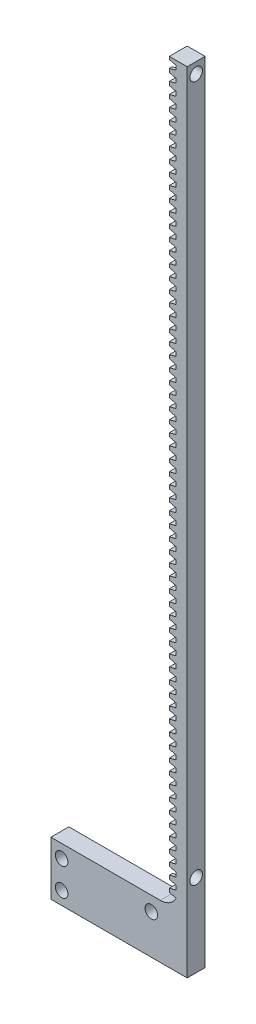
SolidWorks part; units mm, degrees
ref_plane "前视基准面" through (0, 0, 0) normal (0, 0, 1) x (1, 0, 0)
ref_plane "上视基准面" through (0, 0, 0) normal (0, 1, 0) x (1, 0, 0)
ref_plane "右视基准面" through (0, 0, 0) normal (1, 0, 0) x (0, 0, -1)
sketch "草图1" plane through (0, 0, 0) normal (0, 0, 1) x (1, 0, 0)
  line L0 (0, 0) -> (-38, 0)
  line L1 (-38, 0) -> (-38, 15)
  line L2 (-38, 15) -> (-3.0528, 15)
  line L3 (-3, 15) -> (-3, 220) construction
  line L4 (-3, 220) -> (0, 220)
  line L5 (0, 220) -> (0, 0)
  line L6 (-3.0528, 218.7619) -> (-3.0528, 217.6097)
  line L7 (-3.0528, 217.6097) -> (-5, 217.1061)
  line L8 (-5, 217.1061) -> (-5, 216.1239)
  line L9 (-5, 216.1239) -> (-3.0528, 215.6204)
  line L10 (-3.0528, 215.6204) -> (-3.0528, 214.4681)
  line L11 (-3.0528, 214.4681) -> (-5, 213.9645)
  line L12 (-5, 213.9645) -> (-5, 212.9823)
  line L13 (-5, 212.9823) -> (-3.0528, 212.4788)
  line L14 (-3.0528, 212.4788) -> (-3.0528, 211.3265)
  line L15 (-3.0528, 211.3265) -> (-5, 210.8229)
  line L16 (-5, 210.8229) -> (-5, 209.8407)
  line L17 (-5, 209.8407) -> (-3.0528, 209.3372)
  line L18 (-3.0528, 209.3372) -> (-3.0528, 208.1849)
  line L19 (-3.0528, 208.1849) -> (-5, 207.6813)
  line L20 (-5, 207.6813) -> (-5, 206.6992)
  line L21 (-5, 206.6992) -> (-3.0528, 206.1956)
  line L22 (-3.0528, 206.1956) -> (-3.0528, 205.0433)
  line L23 (-3.0528, 205.0433) -> (-5, 204.5397)
  line L24 (-5, 204.5397) -> (-5, 203.5576)
  line L25 (-5, 203.5576) -> (-3.0528, 203.054)
  line L26 (-3.0528, 203.054) -> (-3.0528, 201.9017)
  line L27 (-3.0528, 201.9017) -> (-5, 201.3981)
  line L28 (-5, 201.3981) -> (-5, 200.416)
  line L29 (-5, 200.416) -> (-3.0528, 199.9124)
  line L30 (-3.0528, 199.9124) -> (-3.0528, 198.7601)
  line L31 (-3.0528, 198.7601) -> (-5, 198.2566)
  line L32 (-5, 198.2566) -> (-5, 197.2744)
  line L33 (-5, 197.2744) -> (-3.0528, 196.7708)
  line L34 (-3.0528, 196.7708) -> (-3.0528, 195.6185)
  line L35 (-3.0528, 195.6185) -> (-5, 195.115)
  line L36 (-5, 195.115) -> (-5, 194.1328)
  line L37 (-5, 194.1328) -> (-3.0528, 193.6292)
  line L38 (-3.0528, 193.6292) -> (-3.0528, 192.477)
  line L39 (-3.0528, 192.477) -> (-5, 191.9734)
  line L40 (-5, 191.9734) -> (-5, 190.9912)
  line L41 (-5, 190.9912) -> (-3.0528, 190.4876)
  line L42 (-3.0528, 190.4876) -> (-3.0528, 189.3354)
  line L43 (-3.0528, 189.3354) -> (-5, 188.8318)
  line L44 (-5, 188.8318) -> (-5, 187.8496)
  line L45 (-5, 187.8496) -> (-3.0528, 187.346)
  line L46 (-3.0528, 187.346) -> (-3.0528, 186.1938)
  line L47 (-3.0528, 186.1938) -> (-5, 185.6902)
  line L48 (-5, 185.6902) -> (-5, 184.708)
  line L49 (-5, 184.708) -> (-3.0528, 184.2044)
  line L50 (-3.0528, 184.2044) -> (-3.0528, 183.0522)
  line L51 (-3.0528, 183.0522) -> (-5, 182.5486)
  line L52 (-5, 182.5486) -> (-5, 181.5664)
  line L53 (-5, 181.5664) -> (-3.0528, 181.0628)
  line L54 (-3.0528, 181.0628) -> (-3.0528, 179.9106)
  line L55 (-3.0528, 179.9106) -> (-5, 179.407)
  line L56 (-5, 179.407) -> (-5, 178.4248)
  line L57 (-5, 178.4248) -> (-3.0528, 177.9212)
  line L58 (-3.0528, 177.9212) -> (-3.0528, 176.769)
  line L59 (-3.0528, 176.769) -> (-5, 176.2654)
  line L60 (-5, 176.2654) -> (-5, 175.2832)
  line L61 (-5, 175.2832) -> (-3.0528, 174.7796)
  line L62 (-3.0528, 174.7796) -> (-3.0528, 173.6274)
  line L63 (-3.0528, 173.6274) -> (-5, 173.1238)
  line L64 (-5, 173.1238) -> (-5, 172.1416)
  line L65 (-5, 172.1416) -> (-3.0528, 171.6381)
  line L66 (-3.0528, 171.6381) -> (-3.0528, 170.4858)
  line L67 (-3.0528, 170.4858) -> (-5, 169.9822)
  line L68 (-5, 169.9822) -> (-5, 169)
  line L69 (-5, 169) -> (-3.0528, 168.4965)
  line L70 (-3.0528, 168.4965) -> (-3.0528, 167.3442)
  line L71 (-3.0528, 167.3442) -> (-5, 166.8406)
  line L72 (-5, 166.8406) -> (-5, 165.8585)
  line L73 (-5, 165.8585) -> (-3.0528, 165.3549)
  line L74 (-3.0528, 165.3549) -> (-3.0528, 164.2026)
  line L75 (-3.0528, 164.2026) -> (-5, 163.699)
  line L76 (-5, 163.699) -> (-5, 162.7169)
  line L77 (-5, 162.7169) -> (-3.0528, 162.2133)
  line L78 (-3.0528, 162.2133) -> (-3.0528, 161.061)
  line L79 (-3.0528, 161.061) -> (-5, 160.5574)
  line L80 (-5, 160.5574) -> (-5, 159.5753)
  line L81 (-5, 159.5753) -> (-3.0528, 159.0717)
  line L82 (-3.0528, 159.0717) -> (-3.0528, 157.9194)
  line L83 (-3.0528, 157.9194) -> (-5, 157.4159)
  line L84 (-5, 157.4159) -> (-5, 156.4337)
  line L85 (-5, 156.4337) -> (-3.0528, 155.9301)
  line L86 (-3.0528, 155.9301) -> (-3.0528, 154.7778)
  line L87 (-3.0528, 154.7778) -> (-5, 154.2743)
  line L88 (-5, 154.2743) -> (-5, 153.2921)
  line L89 (-5, 153.2921) -> (-3.0528, 152.7885)
  line L90 (-3.0528, 152.7885) -> (-3.0528, 151.6362)
  line L91 (-3.0528, 151.6362) -> (-5, 151.1327)
  line L92 (-5, 151.1327) -> (-5, 150.1505)
  line L93 (-5, 150.1505) -> (-3.0528, 149.6469)
  line L94 (-3.0528, 149.6469) -> (-3.0528, 148.4947)
  line L95 (-3.0528, 148.4947) -> (-5, 147.9911)
  line L96 (-5, 147.9911) -> (-5, 147.0089)
  line L97 (-5, 147.0089) -> (-3.0528, 146.5053)
  line L98 (-3.0528, 146.5053) -> (-3.0528, 145.3531)
  line L99 (-3.0528, 145.3531) -> (-5, 144.8495)
  line L100 (-5, 144.8495) -> (-5, 143.8673)
  line L101 (-5, 143.8673) -> (-3.0528, 143.3637)
  line L102 (-3.0528, 143.3637) -> (-3.0528, 142.2115)
  line L103 (-3.0528, 142.2115) -> (-5, 141.7079)
  line L104 (-5, 141.7079) -> (-5, 140.7257)
  line L105 (-5, 140.7257) -> (-3.0528, 140.2221)
  line L106 (-3.0528, 140.2221) -> (-3.0528, 139.0699)
  line L107 (-3.0528, 139.0699) -> (-5, 138.5663)
  line L108 (-5, 138.5663) -> (-5, 137.5841)
  line L109 (-5, 137.5841) -> (-3.0528, 137.0805)
  line L110 (-3.0528, 137.0805) -> (-3.0528, 135.9283)
  line L111 (-3.0528, 135.9283) -> (-5, 135.4247)
  line L112 (-5, 135.4247) -> (-5, 134.4425)
  line L113 (-5, 134.4425) -> (-3.0528, 133.9389)
  line L114 (-3.0528, 133.9389) -> (-3.0528, 132.7867)
  line L115 (-3.0528, 132.7867) -> (-5, 132.2831)
  line L116 (-5, 132.2831) -> (-5, 131.3009)
  line L117 (-5, 131.3009) -> (-3.0528, 130.7974)
  line L118 (-3.0528, 130.7974) -> (-3.0528, 129.6451)
  line L119 (-3.0528, 129.6451) -> (-5, 129.1415)
  line L120 (-5, 129.1415) -> (-5, 128.1593)
  line L121 (-5, 128.1593) -> (-3.0528, 127.6558)
  line L122 (-3.0528, 127.6558) -> (-3.0528, 126.5035)
  line L123 (-3.0528, 126.5035) -> (-5, 125.9999)
  line L124 (-5, 125.9999) -> (-5, 125.0177)
  line L125 (-5, 125.0177) -> (-3.0528, 124.5142)
  line L126 (-3.0528, 124.5142) -> (-3.0528, 123.3619)
  line L127 (-3.0528, 123.3619) -> (-5, 122.8583)
  line L128 (-5, 122.8583) -> (-5, 121.8762)
  line L129 (-5, 121.8762) -> (-3.0528, 121.3726)
  line L130 (-3.0528, 121.3726) -> (-3.0528, 120.2203)
  line L131 (-3.0528, 120.2203) -> (-5, 119.7167)
  line L132 (-5, 119.7167) -> (-5, 118.7346)
  line L133 (-5, 118.7346) -> (-3.0528, 118.231)
  line L134 (-3.0528, 118.231) -> (-3.0528, 117.0787)
  line L135 (-3.0528, 117.0787) -> (-5, 116.5751)
  line L136 (-5, 116.5751) -> (-5, 115.593)
  line L137 (-5, 115.593) -> (-3.0528, 115.0894)
  line L138 (-3.0528, 115.0894) -> (-3.0528, 113.9371)
  line L139 (-3.0528, 113.9371) -> (-5, 113.4336)
  line L140 (-5, 113.4336) -> (-5, 112.4514)
  line L141 (-5, 112.4514) -> (-3.0528, 111.9478)
  line L142 (-3.0528, 111.9478) -> (-3.0528, 110.7955)
  line L143 (-3.0528, 110.7955) -> (-5, 110.292)
  line L144 (-5, 110.292) -> (-5, 109.3098)
  line L145 (-5, 109.3098) -> (-3.0528, 108.8062)
  line L146 (-3.0528, 108.8062) -> (-3.0528, 107.654)
  line L147 (-3.0528, 107.654) -> (-5, 107.1504)
  line L148 (-5, 107.1504) -> (-5, 106.1682)
  line L149 (-5, 106.1682) -> (-3.0528, 105.6646)
  line L150 (-3.0528, 105.6646) -> (-3.0528, 104.5124)
  line L151 (-3.0528, 104.5124) -> (-5, 104.0088)
  line L152 (-5, 104.0088) -> (-5, 103.0266)
  line L153 (-5, 103.0266) -> (-3.0528, 102.523)
  line L154 (-3.0528, 102.523) -> (-3.0528, 101.3708)
  line L155 (-3.0528, 101.3708) -> (-5, 100.8672)
  line L156 (-5, 100.8672) -> (-5, 99.885)
  line L157 (-5, 99.885) -> (-3.0528, 99.3814)
  line L158 (-3.0528, 99.3814) -> (-3.0528, 98.2292)
  line L159 (-3.0528, 98.2292) -> (-5, 97.7256)
  line L160 (-5, 97.7256) -> (-5, 96.7434)
  line L161 (-5, 96.7434) -> (-3.0528, 96.2398)
  line L162 (-3.0528, 96.2398) -> (-3.0528, 95.0876)
  line L163 (-3.0528, 95.0876) -> (-5, 94.584)
  line L164 (-5, 94.584) -> (-5, 93.6018)
  line L165 (-5, 93.6018) -> (-3.0528, 93.0982)
  line L166 (-3.0528, 93.0982) -> (-3.0528, 91.946)
  line L167 (-3.0528, 91.946) -> (-5, 91.4424)
  line L168 (-5, 91.4424) -> (-5, 90.4602)
  line L169 (-5, 90.4602) -> (-3.0528, 89.9566)
  line L170 (-3.0528, 89.9566) -> (-3.0528, 88.8044)
  line L171 (-3.0528, 88.8044) -> (-5, 88.3008)
  line L172 (-5, 88.3008) -> (-5, 87.3186)
  line L173 (-5, 87.3186) -> (-3.0528, 86.8151)
  line L174 (-3.0528, 86.8151) -> (-3.0528, 85.6628)
  line L175 (-3.0528, 85.6628) -> (-5, 85.1592)
  line L176 (-5, 85.1592) -> (-5, 84.177)
  line L177 (-5, 84.177) -> (-3.0528, 83.6735)
  line L178 (-3.0528, 83.6735) -> (-3.0528, 82.5212)
  line L179 (-3.0528, 82.5212) -> (-5, 82.0176)
  line L180 (-5, 82.0176) -> (-5, 81.0354)
  line L181 (-5, 81.0354) -> (-3.0528, 80.5319)
  line L182 (-3.0528, 80.5319) -> (-3.0528, 79.3796)
  line L183 (-3.0528, 79.3796) -> (-5, 78.876)
  line L184 (-5, 78.876) -> (-5, 77.8939)
  line L185 (-5, 77.8939) -> (-3.0528, 77.3903)
  line L186 (-3.0528, 77.3903) -> (-3.0528, 76.238)
  line L187 (-3.0528, 76.238) -> (-5, 75.7344)
  line L188 (-5, 75.7344) -> (-5, 74.7523)
  line L189 (-5, 74.7523) -> (-3.0528, 74.2487)
  line L190 (-3.0528, 74.2487) -> (-3.0528, 73.0964)
  line L191 (-3.0528, 73.0964) -> (-5, 72.5929)
  line L192 (-5, 72.5929) -> (-5, 71.6107)
  line L193 (-5, 71.6107) -> (-3.0528, 71.1071)
  line L194 (-3.0528, 71.1071) -> (-3.0528, 69.9548)
  line L195 (-3.0528, 69.9548) -> (-5, 69.4513)
  line L196 (-5, 69.4513) -> (-5, 68.4691)
  line L197 (-5, 68.4691) -> (-3.0528, 67.9655)
  line L198 (-3.0528, 67.9655) -> (-3.0528, 66.8132)
  line L199 (-3.0528, 66.8132) -> (-5, 66.3097)
  line L200 (-5, 66.3097) -> (-5, 65.3275)
  line L201 (-5, 65.3275) -> (-3.0528, 64.8239)
  line L202 (-3.0528, 64.8239) -> (-3.0528, 63.6717)
  line L203 (-3.0528, 63.6717) -> (-5, 63.1681)
  line L204 (-5, 63.1681) -> (-5, 62.1859)
  line L205 (-5, 62.1859) -> (-3.0528, 61.6823)
  line L206 (-3.0528, 61.6823) -> (-3.0528, 60.5301)
  line L207 (-3.0528, 60.5301) -> (-5, 60.0265)
  line L208 (-5, 60.0265) -> (-5, 59.0443)
  line L209 (-5, 59.0443) -> (-3.0528, 58.5407)
  line L210 (-3.0528, 58.5407) -> (-3.0528, 57.3885)
  line L211 (-3.0528, 57.3885) -> (-5, 56.8849)
  line L212 (-5, 56.8849) -> (-5, 55.9027)
  line L213 (-5, 55.9027) -> (-3.0528, 55.3991)
  line L214 (-3.0528, 55.3991) -> (-3.0528, 54.2469)
  line L215 (-3.0528, 54.2469) -> (-5, 53.7433)
  line L216 (-5, 53.7433) -> (-5, 52.7611)
  line L217 (-5, 52.7611) -> (-3.0528, 52.2575)
  line L218 (-3.0528, 52.2575) -> (-3.0528, 51.1053)
  line L219 (-3.0528, 51.1053) -> (-5, 50.6017)
  line L220 (-5, 50.6017) -> (-5, 49.6195)
  line L221 (-5, 49.6195) -> (-3.0528, 49.1159)
  line L222 (-3.0528, 49.1159) -> (-3.0528, 47.9637)
  line L223 (-3.0528, 47.9637) -> (-5, 47.4601)
  line L224 (-5, 47.4601) -> (-5, 46.4779)
  line L225 (-5, 46.4779) -> (-3.0528, 45.9743)
  line L226 (-3.0528, 45.9743) -> (-3.0528, 44.8221)
  line L227 (-3.0528, 44.8221) -> (-5, 44.3185)
  line L228 (-5, 44.3185) -> (-5, 43.3363)
  line L229 (-5, 43.3363) -> (-3.0528, 42.8328)
  line L230 (-3.0528, 42.8328) -> (-3.0528, 41.6805)
  line L231 (-3.0528, 41.6805) -> (-5, 41.1769)
  line L232 (-5, 41.1769) -> (-5, 40.1947)
  line L233 (-5, 40.1947) -> (-3.0528, 39.6912)
  line L234 (-3.0528, 39.6912) -> (-3.0528, 38.5389)
  line L235 (-3.0528, 38.5389) -> (-5, 38.0353)
  line L236 (-5, 38.0353) -> (-5, 37.0532)
  line L237 (-5, 37.0532) -> (-3.0528, 36.5496)
  line L238 (-3.0528, 36.5496) -> (-3.0528, 35.3973)
  line L239 (-3.0528, 35.3973) -> (-5, 34.8937)
  line L240 (-5, 34.8937) -> (-5, 33.9116)
  line L241 (-5, 33.9116) -> (-3.0528, 33.408)
  line L242 (-3.0528, 33.408) -> (-3.0528, 32.2557)
  line L243 (-3.0528, 32.2557) -> (-5, 31.7521)
  line L244 (-5, 31.7521) -> (-5, 30.77)
  line L245 (-5, 30.77) -> (-3.0528, 30.2664)
  line L246 (-3.0528, 30.2664) -> (-3.0528, 29.1141)
  line L247 (-3.0528, 29.1141) -> (-5, 28.6106)
  line L248 (-5, 28.6106) -> (-5, 27.6284)
  line L249 (-5, 27.6284) -> (-3.0528, 27.1248)
  line L250 (-3.0528, 27.1248) -> (-3.0528, 25.9725)
  line L251 (-3.0528, 25.9725) -> (-5, 25.469)
  line L252 (-5, 25.469) -> (-5, 24.4868)
  line L253 (-5, 24.4868) -> (-3.0528, 23.9832)
  line L254 (-3.0528, 23.9832) -> (-3.0528, 22.8309)
  line L255 (-3.0528, 22.8309) -> (-5, 22.3274)
  line L256 (-5, 22.3274) -> (-5, 21.3452)
  line L257 (-5, 21.3452) -> (-3.0528, 20.8416)
  line L258 (-3.0528, 20.8416) -> (-3.0528, 19.6894)
  line L259 (-3.0528, 19.6894) -> (-5, 19.1858)
  line L260 (-5, 19.1858) -> (-5, 18.2036)
  line L261 (-5, 18.2036) -> (-3.0528, 17.7)
  line L262 (-3.0528, 17.7) -> (-3.0528, 16.5478)
  line L263 (-3.0528, 16.5478) -> (-3.0528, 15)
  line L324 (-3, -30) -> (-3, 220) construction
  line L325 (-3, 220) -> (-5, 220)
  line L326 (-5, 220) -> (-5, 219.2655)
  line L327 (-5, 219.2655) -> (-3.0528, 218.7619)
  dimension "D2" = 15
  dimension "D3" = 3
  dimension "D4" = 220
  dimension "D5" = 2
extrude "凸台-拉伸1" add sketch "草图1" along normal blind 5
sketch "草图2" plane through (0, 0, 5) normal (0, 0, 1) x (1, 0, 0)
  line L0 (-38, 7.5) -> (-22.7717, 7.5) construction
  line L1 (-38, 15) -> (-38, 0) construction
  circle A0 centre (-35, 11.3385) radius 1.75
  circle A1 centre (-35, 3.6615) radius 1.75
  circle A2 centre (15, 11) radius 1.75 construction
  circle A3 centre (-10, 11) radius 1.75 construction
  circle A4 centre (15, 11) radius 1.75
  circle A5 centre (-10, 11) radius 1.75
  dimension "D1" = 3.5
  dimension "D2" = 3
extrude "切除-拉伸1" cut sketch "草图2" against normal blind 5
fillet "圆角1" radius 5 1 edges at (-3.0528, 15, 2.5)
sketch "草图3" plane through (0, 0, 0) normal (1, 0, 0) x (0, 0, -1)
  circle A0 centre (-2.5, 213.6024) radius 1.75 construction
  circle A1 centre (-2.5, 23) radius 1.75 construction
  circle A2 centre (-2.5, 217) radius 1.75 construction
  circle A3 centre (-2.5, 23) radius 1.75
  circle A4 centre (-2.5, 217) radius 1.75
  dimension "D1" = 3.5
extrude "切除-拉伸2" cut sketch "草图3" against normal blind 10
